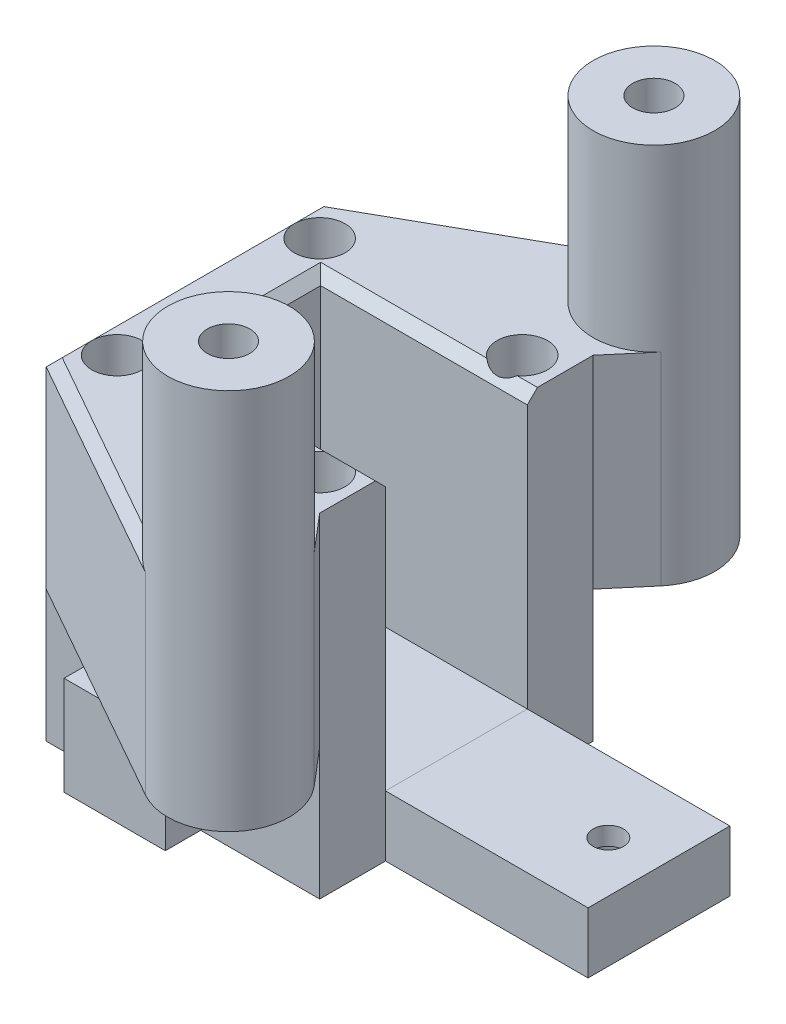
SolidWorks part; units mm, degrees
ref_plane "Front Plane" through (0, 0, 0) normal (0, 0, 1) x (1, 0, 0)
ref_plane "Top Plane" through (0, 0, 0) normal (0, 1, 0) x (1, 0, 0)
ref_plane "Right Plane" through (0, 0, 0) normal (1, 0, 0) x (0, 0, -1)
sketch "Sketch1" plane through (0, 0, 0) normal (0, 1, 0) x (1, 0, 0)
  line L0 (0, 13.5) -> (0, -13.5) construction
  line L5 (13.5, 13.5) -> (-13.5, 13.5)
  line L6 (13.5, 13.5) -> (13.5, -13.5)
  line L7 (13.5, -13.5) -> (-13.5, -13.5)
  line L8 (-13.5, 13.5) -> (-13.5, -13.5)
  line L9 (13.5, 0) -> (-13.5, 0) construction
  line L11 (-10, 10) -> (10, 10) construction
  line L12 (-10, 10) -> (-10, -10) construction
  line L13 (-10, -10) -> (10, -10) construction
  line L14 (10, 10) -> (10, -10) construction
  line L15 (-10, 10) -> (10, -10) construction
  line L16 (-10, -10) -> (10, 10) construction
  point P6 (0, 0)
  dimension "D1" = 27
  dimension "D2" = 27
  dimension "D3" = 20
  dimension "D4" = 20
extrude "Boss-Extrude1" add sketch "Sketch1" along normal blind 13
sketch "Sketch2" plane through (0, 13, 0) normal (0, 1, 0) x (1, 0, 0)
  line L0 (0, -13.5) -> (0, -25.9463) construction
  line L1 (-13.5, -13.5) -> (13.5, -13.5) construction
  line L2 (-13.5, 0) -> (-42.2961, 0) construction
  line L3 (-13.5, 13.5) -> (-13.5, -13.5) construction
  line L4 (13.5, -13.5) -> (13.5, 13.5) construction
  line L5 (-6.9, 7) -> (13.5, 7)
  line L6 (-6.9, 7) -> (-6.9, -7)
  line L7 (-6.9, -7) -> (13.5, -7)
  line L8 (13.5, 7) -> (13.5, -7)
  point P14 (-6.9, 0)
  dimension "D1" = 14
  dimension "D2" = 20.4
extrude "Cut-Extrude1" cut sketch "Sketch2" against normal blind 7
hole_wizard "Ø3.0mm Dowel Hole1" positions "Sketch3" profile "Sketch4" hole size "Ø3.0" standard "ANSI Metric"
sketch "Sketch3" plane through (0, 6, 0) normal (0, 1, 0) x (1, 0, 0)
  line L0 (3.5, 0) -> (13.5, 0) construction
  line L1 (13.5, -7) -> (13.5, 7) construction
  point P0 (3.5, 0)
  dimension "D1" = 10
sketch "Sketch4" plane through (3.5, 6, 0) normal (1, 0, 0) x (0, 0, 1)
  line L0 (0, 0) -> (0, 20.9013)
  line L1 (0, 20.9013) -> (1.5, 20)
  line L2 (1.5, 20) -> (1.5, 0)
  line L5 (1.5, 0) -> (0, 0)
  line L10 (0, 20.9013) -> (-1.5, 20) construction
  line L11 (0, -6.35) -> (0, 107.95) construction
  dimension "Hole Dia." = 3
  dimension "Hole Depth" = 20
  dimension "Drill Angle" = 118
sketch "Sketch5" plane through (0, 0, 0) normal (0, 1, 0) x (1, 0, 0)
  line L0 (-6.9, -7) -> (13.5, -7) construction
  line L1 (13.5, 7) -> (33.5, 7)
  line L2 (13.5, 7) -> (13.5, -7)
  line L3 (13.5, -7) -> (33.5, -7)
  line L4 (33.5, 7) -> (33.5, -7)
  dimension "D1" = 20
extrude "Boss-Extrude2" add sketch "Sketch5" along normal up to surface (6 mm away) separate body up to face at (3.5, 6, 1.5)
hole_wizard "Ø3.0mm Dowel Hole2" positions "Sketch6" profile "Sketch7" hole size "Ø3.0" standard "ANSI Metric"
sketch "Sketch6" plane through (0, 6, 0) normal (0, 1, 0) x (1, 0, 0)
  line L0 (3.5, 0) -> (28.5, 0) construction
  point P0 (28.5, 0)
  dimension "D1" = 25
sketch "Sketch7" plane through (28.5, 6, 0) normal (1, 0, 0) x (0, 0, 1)
  line L0 (0, 0) -> (0, 20.9013)
  line L1 (0, 20.9013) -> (1.5, 20)
  line L2 (1.5, 20) -> (1.5, 0)
  line L5 (1.5, 0) -> (0, 0)
  line L10 (0, 20.9013) -> (-1.5, 20) construction
  line L11 (0, -6.35) -> (0, 107.95) construction
  dimension "Hole Dia." = 3
  dimension "Hole Depth" = 20
  dimension "Drill Angle" = 118
hole_wizard "Ø3.0mm Dowel Hole3" positions "Sketch9" profile "Sketch10" hole size "Ø3.0" standard "ANSI Metric" end condition through all
sketch "Sketch9" plane through (0, 13, 0) normal (0, 1, 0) x (1, 0, 0)
  line L1 (10, -10) -> (-10, -10)
  line L2 (10, -10) -> (10, 10)
  line L3 (10, 10) -> (-10, 10)
  line L4 (-10, -10) -> (-10, 10)
  line L5 (0, -10) -> (0, 0) construction
  line L6 (0, 0) -> (-10, 0) construction
  point P0 (-10, 10)
  point P2 (-10, -10)
  point P9 (10, -10)
  point P10 (10, 10)
  dimension "D1" = 20
  dimension "D2" = 20
  dimension "D3" = 10
  dimension "D4" = 10
sketch "Sketch10" plane through (-10, 13, -10) normal (1, 0, 0) x (0, 0, 1)
  line L0 (0, 0) -> (0, 13)
  line L1 (0, 13) -> (1.5, 13)
  line L2 (1.5, 13) -> (1.5, 0)
  line L5 (1.5, 0) -> (0, 0)
  line L11 (0, -6.35) -> (0, 107.95) construction
  dimension "Thru Hole Dia." = 3
  dimension "Thru Hole Depth" = 13
sketch "Sketch11" plane through (0, 0, 0) normal (0, 1, 0) x (1, 0, 0)
  line L0 (14.5, 0) -> (14.5, 15) construction
  line L1 (13.5, -7) -> (13.5, 7) construction
  line L2 (0, 0) -> (12, 0) construction
  point P7 (12, 21)
  dimension "D1" = 1
  dimension "D2" = 15
  dimension "D3" = 12
  dimension "D4" = 6
sketch "Sketch12" plane through (0, 13, 0) normal (0, 1, 0) x (1, 0, 0)
  circle A0 centre (12, 21) radius 6
  dimension "D1" = 12
extrude "Boss-Extrude3" add sketch "Sketch12" along normal blind 37.7 separate body
sketch "Sketch13" plane through (0, 13, 0) normal (0, 1, 0) x (1, 0, 0)
  line L0 (13.5, 7) -> (13.5, 13.5)
  line L1 (13.5, 13.5) -> (16.5719, 17.1144)
  line L2 (9.0513, 26.2255) -> (-13.5, 13.5)
  line L6 (-13.5, 13.5) -> (-13.5, 0)
  line L7 (-13.5, 13.5) -> (-13.5, -13.5) construction
  line L8 (-13.5, 0) -> (-6.9, 0)
  line L9 (-6.9, 7) -> (-6.9, -7) construction
  line L10 (-6.9, 0) -> (-6.9, 7)
  line L11 (-6.9, 7) -> (13.5, 7)
  circle A1 centre (12, 21) radius 6 construction
  arc A2 (9.0513, 26.2255) -> (16.5719, 17.1144) centre (12, 21) ccw
  circle A3 centre (-10, 10) radius 2.5
  circle A4 centre (10, 10) radius 2.5
  dimension "D1" = 5
  dimension "D2" = 5
extrude "Boss-Extrude4" add sketch "Sketch13" along normal blind 20
pattern_linear "LPattern1" count 2 spacing 42 along (0, 0, 1) of "Boss-Extrude3"
mirror "Mirror5" about plane through (0, 0, 0) normal (0, 0, 1) of "Boss-Extrude4"
hole_wizard "M5x0.8 Tapped Hole2" positions "Sketch16" profile "Sketch17" tap size "M5x0.8" standard "ANSI Metric" end condition through all
sketch "Sketch16" plane through (0, 50.7, 0) normal (0, 1, 0) x (1, 0, 0)
  circle A0 centre (12, 21) radius 6 construction
  circle A1 centre (12, 21) radius 6 construction
  circle A2 centre (12, -21) radius 6 construction
  circle A3 centre (12, -21) radius 6 construction
  point P0 (12, 21)
  point P2 (12, -21)
sketch "Sketch17" plane through (12, 50.7, -21) normal (1, 0, 0) x (0, 0, 1)
  line L0 (0, 0) -> (0, 50.7)
  line L1 (0, 50.7) -> (2.1, 50.7)
  line L2 (2.1, 50.7) -> (2.1, 0)
  line L5 (2.1, 0) -> (0, 0)
  line L11 (0, -6.35) -> (0, 107.95) construction
  dimension "Thru Tap Drill Dia." = 4.2
  dimension "Thru Tap Drill Depth" = 50.7
cosmetic thread "Hole Thread2" parameters "D2"=5
cosmetic thread "Hole Thread3" parameters "D2"=5
chamfer "Chamfer1" distance 1 angle 45 6 edges at (-2.2243, 33, -19.8627) (-13.5, 33, 0) (-2.2243, 33, 19.8627) (3.3, 33, 7) (3.3, 33, -7) (-6.9, 33, 0)
sketch "Sketch18" plane through (0, 0, 13.5) normal (0, 0, 1) x (1, 0, 0)
  line L0 (0, 0) -> (0, 5.75) construction
  line L1 (-5, 8.25) -> (-5, 13)
  line L2 (5, 3.25) -> (-5, 3.25)
  line L3 (5, 3.25) -> (5, 8.25)
  line L4 (5, 8.25) -> (-5, 8.25) construction
  line L5 (-5, 3.25) -> (-5, 8.25)
  line L6 (5, 3.25) -> (-5, 8.25) construction
  line L7 (5, 8.25) -> (-5, 3.25) construction
  line L8 (9.0513, 13) -> (-13.5, 13) construction
  line L9 (-5, 13) -> (5, 13)
  line L10 (5, 13) -> (5, 8.25)
  dimension "D1" = 5.75
  dimension "D2" = 5
  dimension "D3" = 10
extrude "Boss-Extrude5" add sketch "Sketch18" along normal blind 6.74
mirror "Mirror7" about plane through (0, 0, 0) normal (0, 0, 1) of "Boss-Extrude5"
hole_wizard "Hole1" positions "Sketch19" profile "Sketch20" legacy
sketch "Sketch19" plane through (0, 0, 0) normal (0, -1, 0) x (-1, 0, 0)
  point P0 (-3.5, 0)
  point P3 (-28.5, 0)
sketch "Sketch20" plane through (3.5, 0, 0) normal (1, 0, 0) x (0, 0, -1)
  line L0 (0, 0) -> (0, 4.2)
  line L1 (0, 4.2) -> (2.825, 4.2)
  line L2 (2.825, 4.2) -> (2.825, 0)
  line L3 (2.825, 0) -> (0, 0)
  line L4 (0, 110) -> (0, -10) construction
  dimension "Diameter" = 5.65
  dimension "Depth" = 4.2
